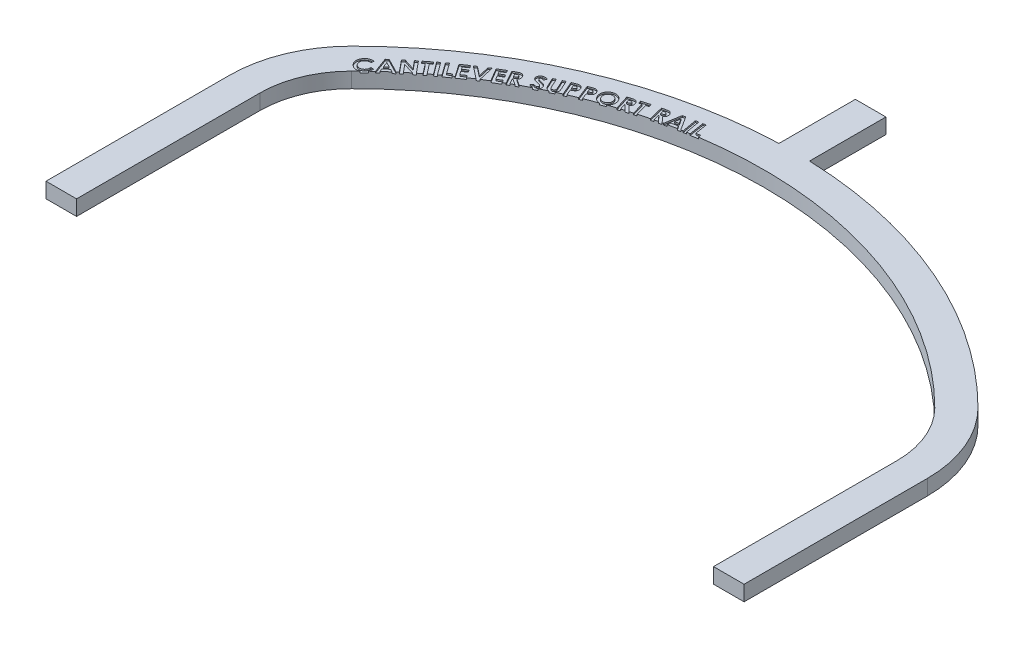
SolidWorks part; units mm, degrees
ref_plane "Front Plane" through (0, 0, 0) normal (0, 0, 1) x (1, 0, 0)
ref_plane "Top Plane" through (0, 0, 0) normal (0, 1, 0) x (1, 0, 0)
ref_plane "Right Plane" through (0, 0, 0) normal (1, 0, 0) x (0, 0, -1)
sketch "Sketch1" plane through (0, 0, 0) normal (0, 1, 0) x (1, 0, 0)
  line L2 (0, 0) -> (0, 233.0006) construction
  line L3 (-12.7, 368.081) -> (-12.7, 431.581)
  line L4 (-12.7, 431.581) -> (12.7, 431.581)
  line L5 (12.7, 431.581) -> (12.7, 368.081)
  line L6 (-260.4274, 260.4274) -> (-242.4669, 242.4669) construction
  line L7 (-290.1854, 36.1854) -> (-264.7854, 36.1854)
  line L8 (-290.1854, 36.1854) -> (-290.1854, 188.5854)
  line L10 (-264.7854, 36.1854) -> (-264.7854, 188.5854)
  line L12 (264.7854, 188.5854) -> (264.7854, 36.1854)
  line L13 (264.7854, 36.1854) -> (290.1854, 36.1854)
  line L14 (290.1854, 188.5854) -> (290.1854, 36.1854)
  line L15 (260.4274, 260.4274) -> (242.4669, 242.4669) construction
  arc A0 (-260.4274, 260.4274) -> (-12.7, 368.081) centre (0, 0) cw
  arc A1 (-242.4669, 242.4669) -> (242.4669, 242.4669) centre (0, 0) cw
  arc A2 (12.7, 368.081) -> (260.4274, 260.4274) centre (0, 0) cw
  arc A3 (-260.4274, 260.4274) -> (-290.1854, 188.5854) centre (-188.5854, 188.5854) ccw
  arc A4 (-242.4669, 242.4669) -> (-264.7854, 188.5854) centre (-188.5854, 188.5854) ccw
  arc A5 (242.4669, 242.4669) -> (264.7854, 188.5854) centre (188.5854, 188.5854) cw
  arc A6 (260.4274, 260.4274) -> (290.1854, 188.5854) centre (188.5854, 188.5854) cw
  point P24 (282.1342, 158.5994)
  dimension "D1" = 342.9
  dimension "D4" = 101.6
  dimension "D2" = 25.4
  dimension "D3" = 152.4
  dimension "D5" = 25.4
  dimension "D6" = 63.5
  dimension "D7" = 45
  dimension "D8" = 45
extrude "Boss-Extrude1" add sketch "Sketch1" along normal blind 12.7
sketch "Sketch2" plane through (0, 12.7, 0) normal (0, 1, 0) x (1, 0, 0)
  text T0 "CANTILEVER SUPPORT RAIL" font "Century Gothic" height 12.7
extrude "Cut-Extrude1" cut sketch "Sketch2" against normal blind 1.27
